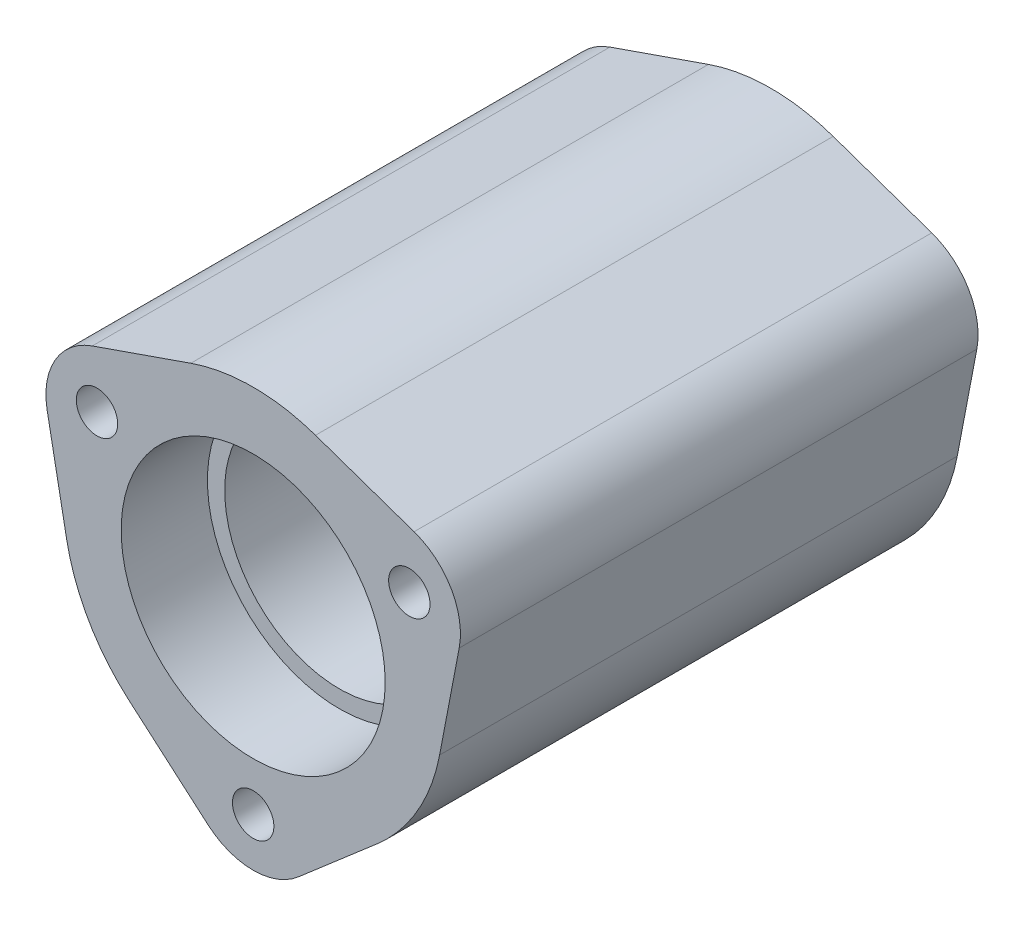
SolidWorks part; units mm, degrees
ref_plane "Спереди" through (0, 0, 0) normal (0, 0, 1) x (1, 0, 0)
ref_plane "Сверху" through (0, 0, 0) normal (0, 1, 0) x (1, 0, 0)
ref_plane "Справа" through (0, 0, 0) normal (1, 0, 0) x (0, 0, -1)
sketch "Эскиз1" plane through (0, 0, 0) normal (0, 0, 1) x (1, 0, 0)
  line L0 (-9.3248, 8.403) -> (-3.6137, 10.3895)
  line L1 (0, 0) -> (0, -9.25) construction
  line L2 (-11.9396, 3.874) -> (-10.8044, -2.0651)
  line L3 (2.6148, -12.277) -> (7.1907, -8.3243)
  line L4 (-2.6148, -12.277) -> (-7.1907, -8.3243)
  line L5 (11.9396, 3.874) -> (10.8044, -2.0651)
  line L6 (9.3248, 8.403) -> (3.6137, 10.3895)
  circle A0 centre (0, 0) radius 11 construction
  arc A1 (7.1907, -8.3243) -> (10.8044, -2.0651) centre (0, 0) ccw
  arc A2 (-9.3248, 8.403) -> (-11.9396, 3.874) centre (-8.0107, 4.625) ccw
  arc A3 (-2.6148, -12.277) -> (2.6148, -12.277) centre (0, -9.25) ccw
  arc A4 (11.9396, 3.874) -> (9.3248, 8.403) centre (8.0107, 4.625) ccw
  arc A5 (3.6137, 10.3895) -> (-3.6137, 10.3895) centre (0, 0) ccw
  arc A6 (-10.8044, -2.0651) -> (-7.1907, -8.3243) centre (0, 0) ccw
  circle A7 centre (0, 0) radius 9.25 construction
  point P24 (0, 0)
  dimension "D1" = 4
  dimension "D2" = 22
  dimension "D3" = 3
  dimension "D4" = 18.5
extrude "тело" add sketch "Эскиз1" along normal mid plane 30
sketch "Эскиз2" plane through (0, 0, 15) normal (0, 0, 1) x (1, 0, 0)
  circle A0 centre (0, 0) radius 7.65
  dimension "D1" = 15.3
extrude "углубление под подшипник" cut sketch "Эскиз2" against normal blind 5
mirror "Углубление под подшипник с обратной стороны" about plane through (0, 0, 0) normal (0, 0, 1) of "углубление под подшипник"
sketch "Эскиз3" plane through (0, 0, 10) normal (0, 0, 1) x (1, 0, 0)
  circle A0 centre (0, 0) radius 6.65
  circle A1 centre (0, 0) radius 7.65 construction
  dimension "D1" = 1
extrude "сквозное отверстие под ось" cut sketch "Эскиз3" against normal through all
sketch "Эскиз4" plane through (0, 0, 15) normal (0, 0, 1) x (1, 0, 0)
  line L0 (0, -13.25) -> (0, -7.65) construction
  circle A0 centre (-9.05, 5.225) radius 1.2
  circle A1 centre (0, -10.45) radius 1.2
  circle A2 centre (9.05, 5.225) radius 1.2
  arc A3 (-2.6148, -12.277) -> (2.6148, -12.277) centre (0, -9.25) ccw construction
  circle A4 centre (0, 0) radius 7.65 construction
  point P8 (0, 0)
  point P18 (0, -10.45)
  dimension "D1" = 2.4
  dimension "D2" = 3
extrude "отверстия для шурупов" cut sketch "Эскиз4" against normal blind 11
mirror "Отверстия для шурупов с другой стороны" about plane through (0, 0, 0) normal (0, 0, 1) of "отверстия для шурупов"
